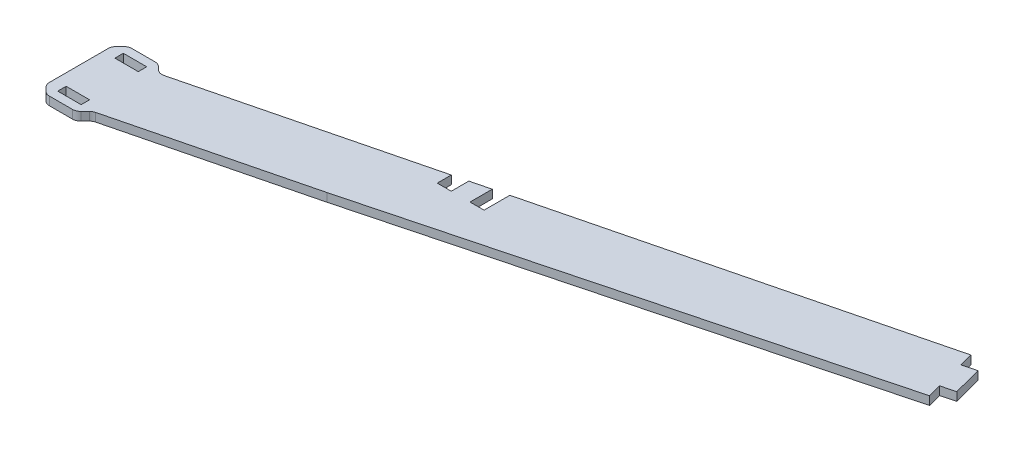
SolidWorks part; units mm, degrees
ref_plane "Front Plane" through (0, 0, 0) normal (0, 0, 1) x (1, 0, 0)
ref_plane "Top Plane" through (0, 0, 0) normal (0, 1, 0) x (1, 0, 0)
ref_plane "Right Plane" through (0, 0, 0) normal (1, 0, 0) x (0, 0, -1)
sketch "Sketch1" plane through (0, 0, 0) normal (0, 1, 0) x (1, 0, 0)
  line L0 (-450, 300) -> (-400, 300)
  line L1 (-400, 300) -> (-200, 250)
  line L2 (-200, 250) -> (200, 250) construction
  line L3 (200, 250) -> (600, 40) construction
  line L4 (600, 40) -> (1200, 40)
  line L5 (-450, -300) -> (-400, -300)
  line L6 (-400, -300) -> (-200, -250)
  line L7 (-200, -250) -> (200, -250) construction
  line L8 (200, -250) -> (600, -40) construction
  line L9 (600, -40) -> (1200, -40)
  line L10 (600, 40) -> (600, -40) construction
  line L11 (200, -250) -> (200, 250) construction
  line L12 (-200, 250) -> (-200, -250) construction
  line L13 (-400, -300) -> (-400, 300) construction
  line L14 (0, 0) -> (200, 0) construction
  line L15 (0, 250) -> (0, 0) construction
  line L16 (1200, 40) -> (1200, -40)
  line L17 (-450, 300) -> (-450, -300)
  line L18 (600, 0) -> (200, 0) construction
  line L19 (-450, 0) -> (-400, 0) construction
  line L20 (-400, 0) -> (-200, 0) construction
  line L21 (-200, 0) -> (0, 0) construction
  line L22 (-200, 250) -> (600, 40)
  line L23 (600, -40) -> (-200, -250)
  dimension "D1" = 600
  dimension "D2" = 200
  dimension "D3" = 50
  dimension "D4" = 400
  dimension "D5" = 500
  dimension "D6" = 80
  dimension "D7" = 600
  dimension "D8" = 400
extrude "Boss-Extrude1" add sketch "Sketch1" along normal blind 15
sketch "Sketch2" plane through (0, 0, 0) normal (0, 0, 1) x (1, 0, 0)
  line L0 (-450, 0) -> (-450, -40)
  line L1 (-450, -40) -> (-400, -40)
  line L2 (-400, -40) -> (-400, 0)
  line L3 (-400, 0) -> (-200, 0) construction
  line L4 (-400, 0) -> (-450, 0)
  line L5 (-440, -15) -> (-440, -40)
  line L6 (-410, -15) -> (-410, -40)
  line L7 (-425, 0) -> (-425, -15) construction
  circle A0 centre (-425, -15) radius 15
  dimension "D1" = 30
  dimension "D2" = 40
extrude "Boss-Extrude2" add sketch "Sketch2" along normal up to surface and the other way up to surface contours L4 L7 A0 L6 L1 L2 | L7 L4 L0 L1 L5 A0 region at (-444.1006, -18.2067, 0) region at (-405.8994, -18.2067, 0) up to face at (-425, 7.5, 300) other way up to face at (-425, 7.5, -300)
sketch "Sketch4" plane through (0, 0, 0) normal (0, 1, 0) x (1, 0, 0)
  line L0 (-450, 230) -> (-400, 230)
  line L1 (-450, 300) -> (-450, -300) construction
  line L2 (-400, 230) -> (-150, 167.5)
  line L3 (-150, 167.5) -> (-150, -167.5)
  line L4 (-150, -167.5) -> (-400, -230)
  line L5 (-400, -230) -> (-450, -230)
  line L6 (-400, 230) -> (-400, -230) construction
  line L7 (-200, 250) -> (-200, -250) construction
  line L9 (-200, 0) -> (-150, 0) construction
  line L10 (-400, -230) -> (-400, -300) construction
  line L11 (-400, -300) -> (-200, -250) construction
  line L12 (-450, 230) -> (-450, -230)
  line L14 (-200, 250) -> (-400, 300) construction
  line L15 (-100, 155) -> (-100, -155)
  line L16 (-100, -155) -> (520, 0)
  line L17 (520, 0) -> (-100, 155)
  line L18 (520, 0) -> (-100, 0) construction
  dimension "D1" = 460
  dimension "D2" = 300
  dimension "D3" = 50
extrude "Cut-Extrude2" cut sketch "Sketch4" against normal through all both and the other way through all
sketch "Sketch5" plane through (0, 0, 0) normal (1, 0, 0) x (0, 0, -1)
  line L0 (-300, 0) -> (-230, 0) construction
  line L1 (-285, 0) -> (-245, 0)
  line L2 (-285, 0) -> (-285, -40)
  line L3 (-285, -40) -> (-245, -40)
  line L4 (-245, 0) -> (-245, -40)
  line L5 (-300, -40) -> (-230, -40) construction
  line L6 (230, 0) -> (300, 0) construction
  line L7 (245, 0) -> (285, 0)
  line L8 (245, 0) -> (245, -40)
  line L9 (245, -40) -> (285, -40)
  line L10 (285, 0) -> (285, -40)
  line L11 (230, -40) -> (300, -40) construction
  line L12 (-300, 0) -> (-300, -40) construction
  line L13 (230, -40) -> (230, 0) construction
  line L14 (300, 0) -> (300, -40) construction
  dimension "D1" = 15
  dimension "D2" = 15
  dimension "D3" = 15
  dimension "D4" = 15
extrude "Cut-Extrude3" cut sketch "Sketch5" against normal through all
sketch "Sketch7" plane through (1200, 0, 0) normal (1, 0, 0) x (0, 0, -1)
  line L1 (-40, 15) -> (-87.5, 50)
  line L2 (-87.5, 50) -> (-87.5, 88.7)
  line L3 (-87.5, 88.7) -> (87.5, 88.7)
  line L4 (87.5, 88.7) -> (87.5, 50)
  line L5 (87.5, 50) -> (40, 15)
  line L7 (-40, 15) -> (40, 15)
  line L8 (-20, 50) -> (-20, 88.7)
  line L9 (87.5, 50) -> (-87.5, 50) construction
  line L10 (0, 88.7) -> (0, 50) construction
  line L11 (-20, 88.7) -> (20, 88.7)
  line L12 (0, 50) -> (0, 0) construction
  line L13 (20, 88.7) -> (20, 50)
  line L14 (-73, 88.7) -> (-63, 88.7)
  line L15 (-73, 88.7) -> (-73, 63.2)
  line L16 (-73, 63.2) -> (-63, 63.2)
  line L17 (-63, 88.7) -> (-63, 63.2)
  line L18 (48.5, 88.7) -> (58.5, 88.7)
  line L19 (48.5, 88.7) -> (48.5, 63.2)
  line L20 (48.5, 63.2) -> (58.5, 63.2)
  line L21 (58.5, 88.7) -> (58.5, 63.2)
  circle A0 centre (0, 50) radius 20
  line M14 (40, 15) -> (-40, 15)
  dimension "D3" = 40
  dimension "D1" = 175
  dimension "D2" = 50
  dimension "D4" = 25.5
  dimension "D5" = 10
  dimension "D6" = 63
  dimension "D7" = 48.5
  dimension "D8" = 38.7
extrude "Boss-Extrude4" add sketch "Sketch7" against normal blind 75 contours L3 L21 L20 L19 L17 L16 L15 L2 L1 L5 L4 M14 region at (1200, 34.0287, 62.6236)
sketch "Sketch8" plane through (0, 0, 0) normal (0, 0, 1) x (1, 0, 0)
  line L0 (1125, 88.7) -> (1200, 88.7) construction
  line L1 (1140, 88.7) -> (1185, 88.7)
  line L2 (1140, 88.7) -> (1140, 15)
  line L3 (1140, 15) -> (1185, 15)
  line L4 (1185, 88.7) -> (1185, 15)
  line L5 (1125, 15) -> (1200, 15) construction
  line L6 (1125, 50) -> (1125, 88.7) construction
  line L7 (1200, 50) -> (1200, 88.7) construction
  line L8 (1155, 88.7) -> (1170, 88.7) construction
  line L9 (1155, 88.7) -> (1170, 88.7)
  line L10 (1155, 88.7) -> (1155, 15)
  line L11 (1155, 15) -> (1170, 15)
  line L12 (1170, 88.7) -> (1170, 15)
  line L15 (1162.5, 50) -> (1162.5, 88.7) construction
  line L16 (1125, 50) -> (1200, 50) construction
  line L17 (1155, 88.7) -> (1170, 88.7) construction
  dimension "D1" = 15
  dimension "D2" = 15
  dimension "D3" = 15
extrude "Cut-Extrude4" cut sketch "Sketch8" against normal through all both and the other way through all contours L10 L1 L2 L3 | L1 L12 L3 L4 region at (1147.5, 51.85, 0) region at (1177.5, 51.85, 0)
fillet "Fillet1" radius 5 53 edges at (1192.5, 50, 87.5) (1162.5, 50, 87.5) (1132.5, 50, 87.5) (1192.5, 50, -87.5) (1162.5, 50, -87.5) (1132.5, 50, -87.5) (1192.5, 88.7, -87.5) (1162.5, 88.7, -87.5) (1132.5, 88.7, -87.5) (1132.5, 88.7, -58.5) (1162.5, 88.7, -58.5) (1192.5, 88.7, -58.5) (1192.5, 88.7, -48.5) (1162.5, 88.7, -48.5) (1132.5, 88.7, -48.5) (1192.5, 88.7, -20) (1162.5, 88.7, -20) (1132.5, 88.7, -20) (1192.5, 88.7, 63) (1162.5, 88.7, 63) (1132.5, 88.7, 63) (1132.5, 88.7, 87.5) (1162.5, 88.7, 87.5) (1192.5, 88.7, 87.5) (1192.5, 88.7, 73) (1162.5, 88.7, 73) (1132.5, 88.7, 73) (1192.5, 88.7, 20) (1162.5, 88.7, 20) (1132.5, 88.7, 20) (600, 7.5, 40) (600, 7.5, -40) (520, 7.5, 0) (-440, -40, -292.5) (-440, -40, -237.5) (-400, -40, -292.5) (-400, -40, -237.5) (-450, -40, -237.5) (-410, -40, -237.5) (-450, -40, -292.5) (-410, -40, -292.5) (-150, 7.5, 167.5) (-100, 7.5, 155) (-150, 7.5, -167.5) (-100, 7.5, -155) (-450, -40, 237.5) (-410, -40, 237.5) (-440, -40, 237.5) (-400, -40, 237.5) (-450, -40, 292.5) (-440, -40, 292.5) (-400, -40, 292.5) (-410, -40, 292.5)
sketch "Sketch9" plane through (0, 0, 0) normal (0, 1, 0) x (1, 0, 0)
  line L35 (-450, -300) -> (-400, -300) construction
  line L36 (-425, -300) -> (-425, -285) construction
  line L37 (-450, 0) -> (0, 0) construction
  line L38 (-437.5, -300) -> (-412.5, -300)
  line L39 (-437.5, -300) -> (-437.5, -285)
  line L56 (1140, -40) -> (1140, -85.466) construction
  line L57 (1200, -40) -> (1185, -40)
  line L58 (1200, -40) -> (1200, -25)
  line L59 (1200, -25) -> (1185, -25)
  line L60 (1185, -40) -> (1185, -25)
  line L61 (1200, 40) -> (1185, 40)
  line L62 (1200, 40) -> (1200, 25)
  line L63 (1200, 25) -> (1185, 25)
  line L64 (1185, 40) -> (1185, 25)
  line L65 (1170, 40) -> (1155, 40)
  line L66 (1170, 40) -> (1170, 25)
  line L67 (1170, 25) -> (1155, 25)
  line L68 (1155, 40) -> (1155, 25)
  line L69 (1140, 40) -> (1125, 40)
  line L70 (1140, 40) -> (1140, 25)
  line L71 (1140, 25) -> (1125, 25)
  line L72 (1125, 40) -> (1125, 25)
  line L73 (1125, -40) -> (1140, -40)
  line L74 (1125, -40) -> (1125, -25)
  line L75 (1125, -25) -> (1140, -25)
  line L76 (1140, -40) -> (1140, -25)
  line L77 (1155, -40) -> (1170, -40)
  line L78 (1155, -40) -> (1155, -25)
  line L79 (1155, -25) -> (1170, -25)
  line L80 (1170, -40) -> (1170, -25)
  line L81 (600.6453, -40) -> (1200, -40) construction
  line L82 (1200, 40) -> (600.6453, 40) construction
  line L83 (1140, 40) -> (1125, 40) construction
  line L84 (1125, 85.466) -> (1125, 40) construction
  line L85 (1140, -25) -> (1155, -25) construction
  line L86 (1170, -25) -> (1185, -25) construction
  line L87 (1185, 25) -> (1170, 25) construction
  line L88 (1155, 25) -> (1140, 25) construction
  line L89 (-437.5, -285) -> (-412.5, -285)
  line L90 (-412.5, -300) -> (-412.5, -285)
  line L92 (-410, -230) -> (-440, -230) construction
  line L93 (-437.5, -230) -> (-412.5, -230)
  line L94 (-437.5, -230) -> (-437.5, -245)
  line L95 (-437.5, -245) -> (-412.5, -245)
  line L96 (-412.5, -230) -> (-412.5, -245)
  line L97 (-425, -245) -> (-400, -245) construction
  line L98 (-425, -285) -> (-425, -245) construction
  line L99 (-425, 285) -> (-425, 245) construction
  line L100 (-425, 300) -> (-425, 285) construction
  line L101 (-450, 300) -> (-400, 300) construction
  line L102 (-412.5, 230) -> (-412.5, 245)
  line L103 (-437.5, 245) -> (-412.5, 245)
  line L104 (-437.5, 230) -> (-437.5, 245)
  line L105 (-437.5, 230) -> (-412.5, 230)
  line L106 (-412.5, 300) -> (-412.5, 285)
  line L107 (-437.5, 285) -> (-412.5, 285)
  line L108 (-437.5, 300) -> (-437.5, 285)
  line L109 (-437.5, 300) -> (-412.5, 300)
  dimension "D1" = 15
  dimension "D2" = 25
  dimension "D3" = 15
extrude "Cut-Extrude5" cut sketch "Sketch9" against normal through all both and the other way through all
sketch "Sketch10" plane through (0, 0, 0) normal (0, 0, 1) x (1, 0, 0)
  line L1 (-450, 15) -> (1200, 15)
  line L2 (-450, 15) -> (-450, 0)
  line L3 (-450, 0) -> (1200, 0)
  line L4 (1200, 15) -> (1200, 0)
  line L5 (-450, 15) -> (-450, -35) construction
  line L6 (-486.0808, 110.0266) -> (1242.84, 110.0266)
  line L7 (-486.0808, 110.0266) -> (-486.0808, -68.8272)
  line L8 (-486.0808, -68.8272) -> (1242.84, -68.8272)
  line L9 (1242.84, 110.0266) -> (1242.84, -68.8272)
  dimension "D1" = 15
extrude "Cut-Extrude6" cut sketch "Sketch10" against normal through all both and the other way through all
sketch "Sketch11" plane through (0, 0, 0) normal (0, 1, 0) x (1, 0, 0)
  line L0 (-450, -315.625) -> (323.7848, -112.5065)
  line L1 (-200, -250) -> (599.3758, -40.1638) construction
  line L2 (-450, -315.625) -> (-450, -242.5)
  line L3 (-450, -230) -> (-450, -300) construction
  line L4 (-450, -242.5) -> (308.1542, -52.9615)
  line L5 (308.1542, -52.9615) -> (323.7848, -112.5065)
  line L6 (-400, -230) -> (-153.7873, -168.4468) construction
  line L7 (-450, -242.5) -> (-450, -230)
  line L8 (-450, -230) -> (-400, -230)
  line L9 (-150, -167.5) -> (-150, -182.5)
  line L10 (-150, -182.5) -> (-135, -182.5)
  line L11 (-135, -182.5) -> (-135, -163.75)
  line L12 (-100, -155) -> (-100, -182.5)
  line L13 (-100, -182.5) -> (-115, -182.5)
  line L14 (-115, -182.5) -> (-115, -158.75)
  line L15 (-100, 148.5961) -> (-100, -148.5961) construction
  line L16 (-150, -163.5961) -> (-150, 163.5961) construction
  line L17 (309.2763, -116.315) -> (305.4678, -101.8065)
  line L18 (-601.3695, -564.0724) -> (1251.3111, -564.0724)
  line L19 (-601.3695, -564.0724) -> (-601.3695, 511.8547)
  line L20 (-601.3695, 511.8547) -> (1251.3111, 511.8547)
  line L21 (1251.3111, -564.0724) -> (1251.3111, 511.8547)
  line L22 (305.4678, -101.8065) -> (319.9763, -97.998)
  line L23 (293.6011, -56.5997) -> (297.4095, -71.1082)
  line L24 (297.4095, -71.1082) -> (311.918, -67.2997)
  line L25 (305.4678, -101.8065) -> (297.4095, -71.1082) construction
  dimension "D1" = 800
  dimension "D2" = 15
  dimension "D3" = 15
  dimension "D4" = 15
  dimension "D5" = 15
extrude "Cut-Extrude9" cut sketch "Sketch11" against normal through all and the other way through all contours L18 L21 L20 L19 L7 L8 L4 L5 L0 L2 | L10 L11 L4 L9 | L14 L13 L12 L4 | L22 L17 L0 L5 | L23 L24 L5 L4 region at (314.6263, 0, 107.1565) region at (-142.2222, 0, 174.0278) region at (302.7564, 0, 61.9959) region at (-107.3171, 0, 169.6646) region at (335.9065, 0, 21.8353)
sketch "Sketch12" plane through (0, 0, 0) normal (0, 0, 1) x (1, 0, 0)
  line L1 (-450, 15) -> (319.9763, 15)
  line L2 (-450, 15) -> (-450, 9)
  line L3 (-450, 9) -> (319.9763, 9)
  line L4 (319.9763, 15) -> (319.9763, 9)
  line L6 (-450, 15) -> (-437.5, 15) construction
  line L7 (319.9763, 0) -> (319.9763, 15) construction
  line L8 (-450, 15) -> (-450, 0) construction
  line L9 (-437.5, 0) -> (-412.5, 0) construction
  dimension "D1" = 9
extrude "Cut-Extrude10" cut sketch "Sketch12" against normal through all both and the other way through all
sketch "Sketch13" plane through (0, 9, 0) normal (0, 1, 0) x (1, 0, 0)
  line L0 (-412.5, -230) -> (-412.5, -245) construction
  line L1 (-437.5, -245) -> (-412.5, -245)
  line L2 (-437.5, -245) -> (-437.5, -239)
  line L3 (-437.5, -239) -> (-412.5, -239)
  line L4 (-412.5, -245) -> (-412.5, -239)
  line L5 (-412.5, -285) -> (-412.5, -300) construction
  line L6 (-437.5, -285) -> (-412.5, -285)
  line L7 (-437.5, -285) -> (-437.5, -291)
  line L8 (-437.5, -291) -> (-412.5, -291)
  line L9 (-412.5, -285) -> (-412.5, -291)
  line L10 (-412.5, -300) -> (-400, -300) construction
  line L11 (-400, -230) -> (-412.5, -230) construction
  dimension "D1" = 9
  dimension "D2" = 9
extrude "Boss-Extrude5" add sketch "Sketch13" against normal up to surface (9 mm away) up to face at (-172.5612, 0, 198.7158)
sketch "Sketch14" plane through (0, 9, 0) normal (0, 1, 0) x (1, 0, 0)
  line L0 (-450, -300) -> (-450, -230) construction
  line L1 (-450, -309) -> (-400, -309)
  line L2 (-450, -309) -> (-450, -221)
  line L3 (-450, -221) -> (-400, -221)
  line L4 (-400, -309) -> (-400, -221)
  line L5 (-437.5, -291) -> (-412.5, -291)
  line L6 (-437.5, -291) -> (-437.5, -300)
  line L7 (-437.5, -300) -> (-412.5, -300)
  line L8 (-412.5, -291) -> (-412.5, -300)
  line L9 (-437.5, -239) -> (-412.5, -239)
  line L10 (-437.5, -239) -> (-437.5, -230)
  line L11 (-437.5, -230) -> (-412.5, -230)
  line L12 (-412.5, -239) -> (-412.5, -230)
  line L13 (-400, -300) -> (-409, -309)
  line L14 (-400, -230) -> (-409, -221)
  line L15 (-400, -230) -> (-412.5, -230) construction
  line L16 (-450, -300) -> (-441, -309)
  line L17 (-450, -230) -> (-441, -221)
  line M16 (-412.5, -300) -> (-400, -300)
  line M33 (-400, -230) -> (-412.5, -230)
  line M37 (-437.5, -230) -> (-450, -230)
  line M39 (-450, -300) -> (-437.5, -300)
  dimension "D1" = 9
  dimension "D2" = 9
  dimension "D3" = 45
  dimension "D4" = 45
  dimension "D5" = 45
  dimension "D6" = 45
extrude "Boss-Extrude6" add sketch "Sketch14" against normal up to surface (9 mm away) contours L13 L7 L2 L1 M16 M39 | L14 L3 L2 L11 M33 M37 region at (-425, 9, 304.1707) region at (-425, 9, 225.8293) up to face at (-172.5612, 0, 198.7158)
fillet "Fillet2" radius 9 8 edges at (-450, 4.5, 300) (-409, 4.5, 221) (-450, 4.5, 230) (-441, 4.5, 221) (-400, 4.5, 230) (-441, 4.5, 309) (-400, 4.5, 300) (-409, 4.5, 309)
